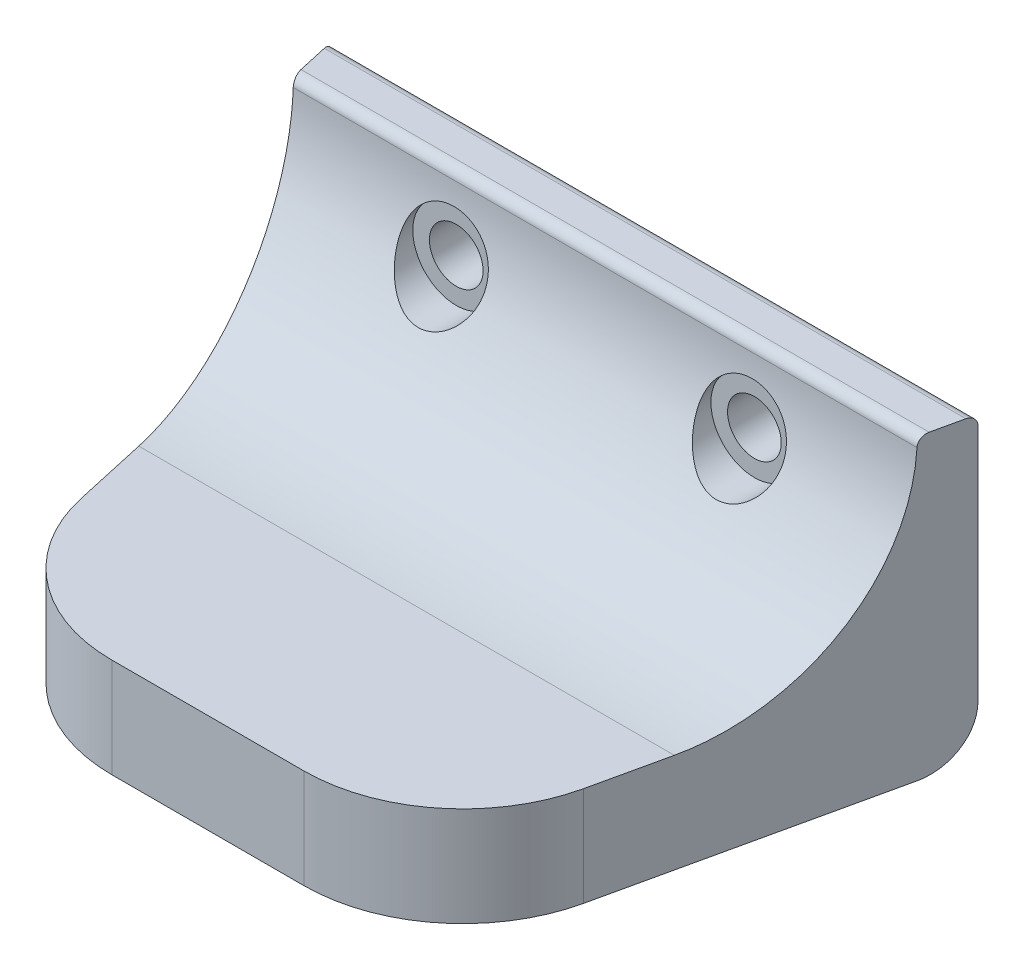
SolidWorks part; units mm, degrees
material "Markforged Onyx"
ref_plane "Front Plane" through (0, 0, 0) normal (0, 0, 1) x (1, 0, 0)
ref_plane "Top Plane" through (0, 0, 0) normal (0, 1, 0) x (1, 0, 0)
ref_plane "Right Plane" through (0, 0, 0) normal (1, 0, 0) x (0, 0, -1)
sketch "Sketch1" plane through (0, 0, 0) normal (0, 1, 0) x (1, 0, 0)
  line L0 (-41.275, 28.575) -> (-28.575, -28.575)
  line L1 (-41.275, -28.575) -> (41.275, -28.575) construction
  line L2 (-41.275, -28.575) -> (-41.275, 28.575) construction
  line L3 (-41.275, 28.575) -> (41.275, 28.575) construction
  line L4 (41.275, -28.575) -> (41.275, 28.575) construction
  line L5 (-41.275, -28.575) -> (41.275, 28.575) construction
  line L6 (-41.275, 28.575) -> (41.275, -28.575) construction
  line L7 (-28.575, -28.575) -> (28.575, -28.575)
  line L8 (28.575, -28.575) -> (41.275, 28.575)
  line L9 (0, 28.575) -> (0, -28.575) construction
  line L10 (-41.275, 28.575) -> (41.275, 28.575)
  line L11 (-39.8639, 22.225) -> (39.8639, 22.225)
  point P0 (0, 0)
  dimension "D1" = 82.55
  dimension "D2" = 57.15
  dimension "D3" = 57.15
  dimension "D4" = 6.35
extrude "Boss-Extrude1" add sketch "Sketch1" along normal blind 12.7 contours L11 L0 L7 L8 | L0 L11 L8 L10 region at (0, 0, -25.4184) region at (0, 0, 1.7784)
extrude "Boss-Extrude2" add sketch "Sketch1<5>" along normal blind 38.1 contours L0 L11 L8 L10 region at (0, 0, -25.4184)
sketch "Sketch1<5>" plane through (0, 0, 0) normal (0, 1, 0) x (1, 0, 0) same geometry as "Sketch1"
fillet "Fillet1" radius 25.4 1 edges at (0, 12.7, -22.225)
fillet "Fillet2" radius 20.32 2 edges at (28.575, 6.35, 28.575) (-28.575, 6.35, 28.575)
fillet "Fillet3" radius 6.35 1 edges at (0, 0, -28.575)
sketch "Sketch3" plane through (0, 0, -28.575) normal (0, 0, -1) x (-1, 0, 0)
  line L0 (41.275, 22.225) -> (-41.275, 22.225) construction
  line L1 (41.275, 38.1) -> (41.275, 6.35) construction
  line L2 (-41.275, 38.1) -> (-41.275, 6.35) construction
fillet "Fillet4" radius 1.27 2 edges at (0, 38.1, -22.225) (0, 38.1, -28.575)
sketch "Sketch6" plane through (0, 0, -28.575) normal (0, 0, -1) x (-1, 0, 0)
  line L1 (-41.275, 28.702) -> (41.275, 28.702) construction
  line L2 (-41.275, 36.83) -> (-41.275, 6.35) construction
  line L3 (41.275, 36.83) -> (41.275, 6.35) construction
  line L4 (-41.275, 6.35) -> (41.275, 6.35) construction
  line L5 (0, 0) -> (0, 28.702) construction
  circle A0 centre (-19.05, 28.702) radius 3.429
  circle A1 centre (-19.05, 28.702) radius 5.5563 construction
  circle A2 centre (19.05, 28.702) radius 5.5563 construction
  circle A3 centre (19.05, 28.702) radius 3.429
  dimension "D2" = 6.858
  dimension "D1" = 22.352
  dimension "D4" = 38.1
  dimension "D3" = 2.1273
extrude "Cut-Extrude5" cut sketch "Sketch6" against normal up to surface (8.1526 mm away) up to face at (0, 22.256, -11.9316)
ref_plane "Plane2" through (0, 0, -22.225) normal (0, 0, -1) x (-1, 0, 0)
sketch "Sketch7" plane through (0, 0, -22.225) normal (0, 0, -1) x (-1, 0, 0)
  circle A0 centre (-19.05, 28.702) radius 5.5563 construction
  circle A1 centre (-19.05, 28.702) radius 5.5563
  circle A2 centre (19.05, 28.702) radius 5.5563 construction
  circle A3 centre (19.05, 28.702) radius 5.5563
extrude "Cut-Extrude6" cut sketch "Sketch7" against normal up to surface (1.8026 mm away) up to face at (22.3673, 29.5701, -20.7499)
